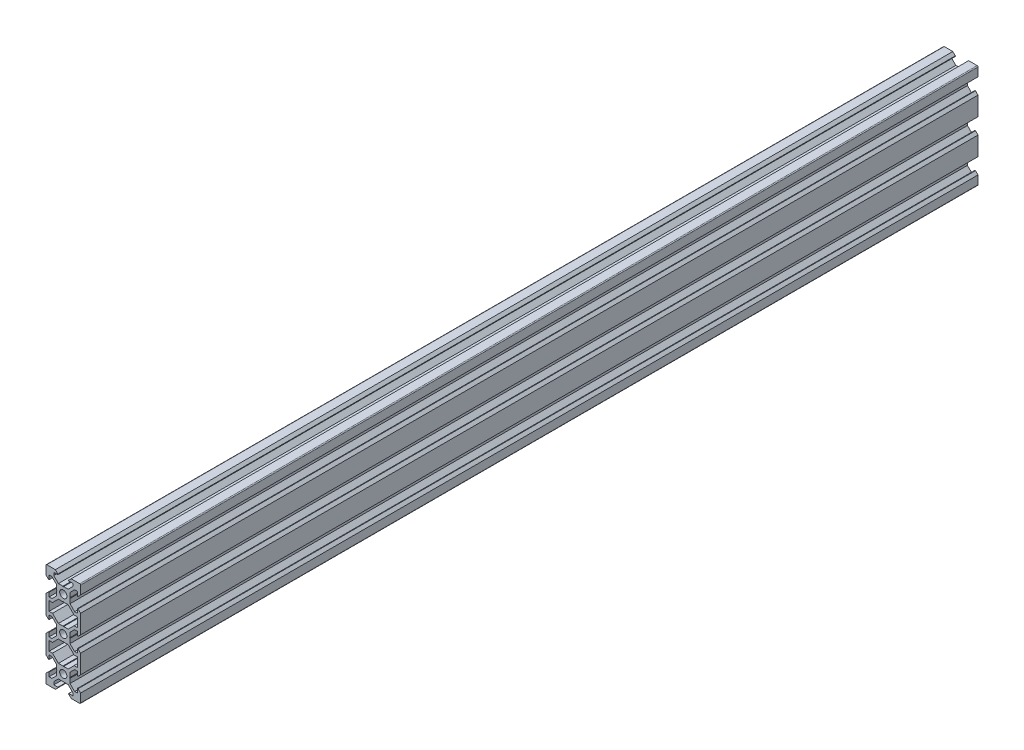
SolidWorks part; units mm, degrees
ref_plane "Plan de face" through (0, 0, 0) normal (0, 0, 1) x (1, 0, 0)
ref_plane "Plan de dessus" through (0, 0, 0) normal (0, 1, 0) x (1, 0, 0)
ref_plane "Plan de droite" through (0, 0, 0) normal (1, 0, 0) x (0, 0, -1)
ref_axis "Axe" through (0, 0, -13.782) along (0, 0, 1)
sketch "Esquisse1" plane through (0, 0, 0) normal (0, 0, 1) x (1, 0, 0)
  line L0 (0, 27.6392) -> (0, -27.6392) construction
  line L1 (-33.6074, 0) -> (33.6074, 0) construction
  line L2 (0, 0) -> (-22.2114, 22.2114) construction
  line L3 (-9.5, 10) -> (-4.58, 10)
  line L4 (-4.58, 10) -> (-3.125, 8.545)
  line L5 (-3.125, 8.545) -> (-3.125, 8.2)
  line L6 (-3.125, 8.2) -> (-5.5, 8.2)
  line L7 (-2.8393, 3.9) -> (-5.5, 6.5607)
  line L8 (-2.8393, 3.9) -> (-0.21, 3.9)
  line L9 (-5.5, 6.5607) -> (-5.5, 8.2)
  line L10 (0, 3.69) -> (0, 2.1)
  line L11 (-3.9, 2.8393) -> (-6.5607, 5.5)
  line L12 (-8.545, 3.125) -> (-8.2, 3.125)
  line L13 (-8.2, 3.125) -> (-8.2, 5.5)
  line L14 (-6.5607, 5.5) -> (-8.2, 5.5)
  line L15 (-10, 4.58) -> (-8.545, 3.125)
  line L16 (-10, 9.5) -> (-10, 4.58)
  line L17 (-0.21, 3.9) -> (0, 3.69)
  line L18 (-3.9, 2.8393) -> (-3.9, 0.21)
  line L19 (-6.2393, -12.7) -> (-8.2, -12.7)
  line L20 (-3.9, 0.21) -> (-3.69, 0)
  line L21 (-0.21, -3.9) -> (0, -3.69)
  line L22 (0, -3.69) -> (0, -2.1)
  line L23 (-6.5607, -5.5) -> (-8.2, -5.5)
  line L24 (-2.8393, -3.9) -> (-0.21, -3.9)
  line L25 (-8.545, -3.125) -> (-8.2, -3.125)
  line L26 (-10, -4.58) -> (-8.545, -3.125)
  line L27 (-8.2, -3.125) -> (-8.2, -5.5)
  line L28 (-2.8393, -3.9) -> (-6.2393, -7.3)
  line L29 (-3.9, -2.8393) -> (-6.5607, -5.5)
  line L30 (-3.9, -2.8393) -> (-3.9, -0.21)
  line L31 (-3.9, -0.21) -> (-3.69, 0)
  line L32 (-6.2393, -7.3) -> (-8.2, -7.3)
  line L33 (-8.2, -7.3) -> (-8.2, -12.7)
  line L34 (-8.2, -10) -> (-10, -10) construction
  line L35 (-10, -15.42) -> (-10, -4.58)
  line L36 (-3.9, -19.79) -> (-3.69, -20)
  line L37 (-3.9, -17.1607) -> (-3.9, -19.79)
  line L38 (-3.9, -17.1607) -> (-6.5607, -14.5)
  line L39 (-2.8393, -16.1) -> (-6.2393, -12.7)
  line L40 (-8.2, -16.875) -> (-8.2, -14.5)
  line L41 (-10, -15.42) -> (-8.545, -16.875)
  line L42 (-8.545, -16.875) -> (-8.2, -16.875)
  line L43 (-2.8393, -16.1) -> (-0.21, -16.1)
  line L44 (-6.5607, -14.5) -> (-8.2, -14.5)
  line L45 (0, -16.31) -> (0, -17.9)
  line L46 (-0.21, -16.1) -> (0, -16.31)
  line L47 (-8.2, -30) -> (-10, -30) construction
  line L48 (-3.69, -20) -> (0, -20) construction
  line L49 (-0.21, -23.9) -> (0, -23.69)
  line L50 (0, -23.69) -> (0, -22.1)
  line L51 (-6.5607, -25.5) -> (-8.2, -25.5)
  line L52 (-2.8393, -23.9) -> (-0.21, -23.9)
  line L53 (-8.545, -23.125) -> (-8.2, -23.125)
  line L54 (-10, -24.58) -> (-8.545, -23.125)
  line L55 (-8.2, -23.125) -> (-8.2, -25.5)
  line L56 (-2.8393, -23.9) -> (-6.2393, -27.3)
  line L57 (-3.9, -22.8393) -> (-6.5607, -25.5)
  line L58 (-3.9, -22.8393) -> (-3.9, -20.21)
  line L59 (-3.9, -20.21) -> (-3.69, -20)
  line L60 (-10, -24.58) -> (-10, -35.42)
  line L61 (-8.2, -32.7) -> (-8.2, -27.3)
  line L62 (-6.2393, -32.7) -> (-8.2, -32.7)
  line L63 (-3.9, -39.79) -> (-3.69, -40)
  line L64 (-3.9, -37.1607) -> (-3.9, -39.79)
  line L65 (-3.9, -37.1607) -> (-6.5607, -34.5)
  line L66 (-2.8393, -36.1) -> (-6.2393, -32.7)
  line L67 (-8.2, -36.875) -> (-8.2, -34.5)
  line L68 (-10, -35.42) -> (-8.545, -36.875)
  line L69 (-8.545, -36.875) -> (-8.2, -36.875)
  line L70 (-2.8393, -36.1) -> (-0.21, -36.1)
  line L71 (-6.5607, -34.5) -> (-8.2, -34.5)
  line L72 (0, -36.31) -> (0, -37.9)
  line L73 (-0.21, -36.1) -> (0, -36.31)
  line L74 (-3.9, -40.21) -> (-3.69, -40)
  line L75 (-6.2393, -27.3) -> (-8.2, -27.3)
  line L76 (-3.9, -42.8393) -> (-3.9, -40.21)
  line L77 (-0.21, -43.9) -> (0, -43.69)
  line L78 (-10, -49.5) -> (-10, -44.58)
  line L79 (-10, -44.58) -> (-8.545, -43.125)
  line L80 (-6.5607, -45.5) -> (-8.2, -45.5)
  line L81 (-8.2, -43.125) -> (-8.2, -45.5)
  line L82 (-8.545, -43.125) -> (-8.2, -43.125)
  line L83 (-3.9, -42.8393) -> (-6.5607, -45.5)
  line L84 (0, -43.69) -> (0, -42.1)
  line L85 (-5.5, -46.5607) -> (-5.5, -48.2)
  line L86 (-2.8393, -43.9) -> (-0.21, -43.9)
  line L87 (-2.8393, -43.9) -> (-5.5, -46.5607)
  line L88 (-3.125, -48.2) -> (-5.5, -48.2)
  line L89 (-3.125, -48.545) -> (-3.125, -48.2)
  line L90 (-4.58, -50) -> (-3.125, -48.545)
  line L91 (-9.5, -50) -> (-4.58, -50)
  arc A0 (0, -2.1) -> (0, 2.1) centre (0, 0) cw
  arc A1 (-9.5, 10) -> (-10, 9.5) centre (-9.5, 9.5) ccw
  arc A2 (0, -37.9) -> (0, -42.1) centre (0, -40) ccw
  arc A3 (-9.5, -50) -> (-10, -49.5) centre (-9.5, -49.5) cw
  arc A4 (0, -17.9) -> (0, -22.1) centre (0, -20) ccw
  point P4 (0, 0)
  point P7 (0, 0)
  point P30 (-10, 10)
  point P60 (0, -20)
  point P111 (-10, -50)
  dimension "D5" = 11
  dimension "D2" = 2.1
  dimension "D3" = 6.25
  dimension "D10" = 0.5
  dimension "D4" = 9.16
  dimension "D6" = 1.5
  dimension "D7" = 1.8
  dimension "D8" = 4.3
  dimension "D9" = 20
  dimension "D11" = 0.42
  dimension "D12" = 10
  dimension "D13" = 1.8
extrude "Boss.-Extru.1" add sketch "Esquisse1" along normal blind 519.38
sketch "Esquisse3" plane through (0, 0, 519.38) normal (0, 0, 1) x (1, 0, 0)
  line L0 (0, 0) -> (-9.8536, 9.8536) construction
  line L1 (-8.2, 8.2) -> (-8.2, 6.57)
  line L2 (-8.2, 6.57) -> (-7.54, 6.57)
  line L3 (-7.54, 6.57) -> (-6.57, 7.54)
  line L4 (-8.2, 3.125) -> (-8.2, 5.5) construction
  line L5 (-6.57, 8.2) -> (-6.57, 7.54)
  line L6 (-8.2, 8.2) -> (-6.57, 8.2)
  line L7 (-5.5, 6.5607) -> (-5.5, 8.2) construction
  line L8 (-3.69, -20) -> (0, -20) construction
  line L9 (-8.2, -48.2) -> (-6.57, -48.2)
  line L10 (-6.57, -48.2) -> (-6.57, -47.54)
  line L11 (-7.54, -46.57) -> (-6.57, -47.54)
  line L12 (-8.2, -46.57) -> (-7.54, -46.57)
  line L13 (-8.2, -48.2) -> (-8.2, -46.57)
  arc A0 (-9.5, 10) -> (-10, 9.5) centre (-9.5, 9.5) ccw construction
  point P13 (-7.055, 7.055)
  point P14 (-6.57, 7.87)
  point P26 (-7.055, -47.055)
  dimension "D1" = 1.07
extrude "Enlèv. mat.-Extru.1" [suppressed] cut sketch "Esquisse3" against normal through all
mirror "Symétrie1" about plane through (0, 3.69, 519.38) normal (-1, 0, 0) of "Enlèv. mat.-Extru.1", "Boss.-Extru.1"
